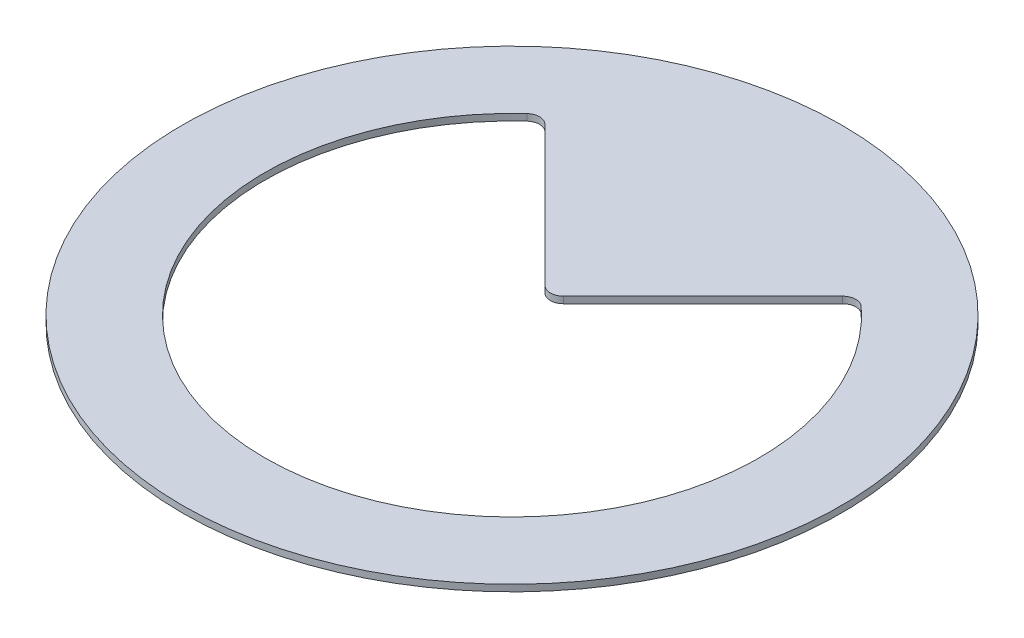
SolidWorks part; units mm, degrees
ref_plane "Front" through (0, 0, 0) normal (0, 0, 1) x (1, 0, 0)
ref_plane "Top" through (0, 0, 0) normal (0, 1, 0) x (1, 0, 0)
ref_plane "Right" through (0, 0, 0) normal (1, 0, 0) x (0, 0, -1)
sketch "Sketch1" plane through (0, 0, 0) normal (0, 1, 0) x (1, 0, 0)
  line L1 (0, 55.799) -> (0, -37.5) construction
  line L3 (-23.8984, 28.8984) -> (0, 5)
  line L4 (0, 5) -> (23.8984, 28.8984)
  line L5 (0, -50) -> (0, -56.3751) construction
  arc A2 (-23.8984, 28.8984) -> (23.8984, 28.8984) centre (0, 0) ccw
  circle A3 centre (0, 0) radius 50
  dimension "D1" = 100
  dimension "D3" = 75
  dimension "D4" = 90
  dimension "D5" = 5
extrude "Boss-Extrude1" add sketch "Sketch1" along normal blind 1
fillet "Fillet1" radius 2 3 edges at (-23.8984, 0.5, -28.8984) (23.8984, 0.5, -28.8984) (0, 0.5, -5)
